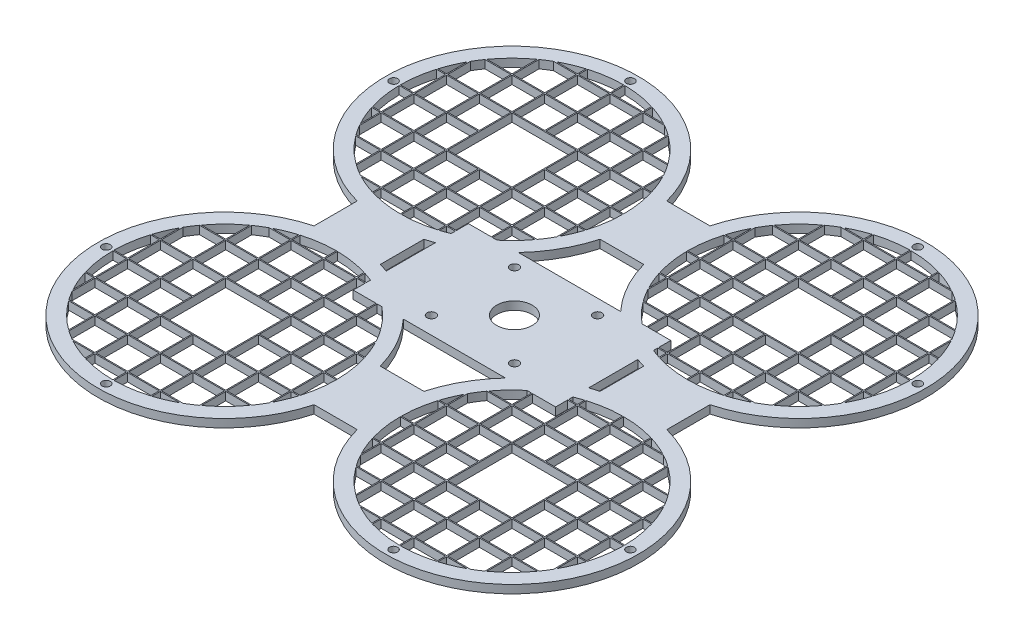
SolidWorks part; units mm, degrees
ref_plane "Front Plane" through (0, 0, 0) normal (0, 0, 1) x (1, 0, 0)
ref_plane "Top Plane" through (0, 0, 0) normal (0, 1, 0) x (1, 0, 0)
ref_plane "Right Plane" through (0, 0, 0) normal (1, 0, 0) x (0, 0, -1)
sketch "Sketch2" plane through (0, 0, 0) normal (0, 1, 0) x (1, 0, 0)
  circle A1 centre (0, 0) radius 41
  circle A2 centre (0, 0) radius 46
  point P208 (0, 0)
extrude "Boss-Extrude2" add sketch "Sketch2" along normal blind 3
sketch "Sketch4" plane through (0, 3, 0) normal (0, 1, 0) x (1, 0, 0)
  line L0 (0, 46) -> (0, 12)
  line L1 (12, 44.4072) -> (12, -44.4072)
  line L2 (24, 39.2428) -> (24, -39.2428)
  line L3 (36, 28.6356) -> (36, -28.6356)
  line L4 (-12, 44.4072) -> (-12, -44.4072)
  line L5 (-24, 39.2428) -> (-24, -32)
  line L6 (-36, 28.6356) -> (-36, -28.6356)
  line L7 (-46, 0) -> (-12, 0)
  line L8 (-44.4072, -12) -> (44.4072, -12)
  line L9 (-39.2428, -24) -> (39.2428, -24)
  line L10 (12, 0) -> (46, 0)
  line L11 (-44.4072, 12) -> (44.4072, 12)
  line L12 (-39.2428, 24) -> (39.2428, 24)
  line L13 (-28.6356, 36) -> (28.6356, 36)
  line L14 (-16, -36) -> (28.6356, -36)
  line L15 (0, -12) -> (0, -46)
  line L50 (-26.0661, -32) -> (-16, -32)
  line L52 (-26.0661, -32) -> (-26.0661, -37.902)
  line L60 (-16, -32) -> (-16, -43.1277)
  line L61 (-28.6356, -36) -> (-26.0661, -36) [skipped]
  circle A1 centre (0, 0) radius 46 construction
  circle A2 centre (0, 0) radius 46
  dimension "D1" = 4
  dimension "D2" = 4
extrude "Extrude-Thin5" add sketch "Sketch4" against normal blind 3 thin thin type one direction wall 0.4
sketch "Sketch5" plane through (0, 0, 0) normal (0, -1, 0) x (1, 0, 0)
  circle A0 centre (0, -43.4524) radius 1.5
  circle A3 centre (43.4524, 0) radius 1.5
  circle A4 centre (0, 43.4524) radius 1.5 [skipped]
  circle A5 centre (-43.4524, 0) radius 1.5 [skipped]
  point P11 (0, 0)
  dimension "D1" = 4
extrude "Cut-Extrude1" cut sketch "Sketch5" against normal blind 3
sketch "Sketch8" plane through (0, 3, 0) normal (0, 1, 0) x (1, 0, 0)
  line L1 (-16, -32) -> (-25.632, -32)
  line L2 (-16, -32) -> (-16, -37.7492)
  line L3 (-16, -37.7492) -> (-25.632, -37.7492)
  line L4 (-25.632, -32) -> (-25.632, -37.7492)
extrude "Boss-Extrude4" add sketch "Sketch8" against normal through all
sketch "Sketch9" plane through (0, 3, 0) normal (0, 1, 0) x (1, 0, 0)
  circle A3 centre (-22.2697, -36.1812) radius 2.25
extrude "Cut-Extrude3" cut sketch "Sketch9" against normal through all
ref_plane "Plane1" through (-52.73, 0, 0) normal (1, 0, 0) x (0, 0, -1)
mirror "Mirror1" about plane through (-52.73, 0, 0) normal (1, 0, 0) of bodies 159
sketch "Sketch10" plane through (0, 3, 0) normal (0, 1, 0) x (1, 0, 0)
  line L0 (-66.2554, 12) -> (-69.06, 12) construction
  line L1 (-63.5152, 12) -> (-41.7915, 12)
  line L2 (-63.5152, 12) -> (-63.5152, -12.4)
  line L3 (-63.5152, -12.4) -> (-41.7915, -12.4)
  line L4 (-41.7915, 12) -> (-41.7915, -12.4)
  line L5 (-66.3801, -12.4) -> (-69.06, -12.4) construction
extrude "Boss-Extrude5" add sketch "Sketch10" against normal up to surface (3 mm away) up to face at (-22.2697, 0, 38.4312)
ref_plane "Plane2" through (0, 0, 52.73) normal (0, 0, 1) x (1, 0, 0)
mirror "Mirror2" about plane through (0, 0, 52.73) normal (0, 0, 1) of bodies 177
sketch "Sketch11" plane through (0, 3, 0) normal (0, 1, 0) x (1, 0, 0)
  line L0 (-93.06, -36.4) -> (-93.06, -39.0799) construction
  line L1 (-117.46, -41.6571) -> (-93.06, -41.6571)
  line L2 (-117.46, -41.6571) -> (-117.46, -63.409)
  line L3 (-117.46, -63.409) -> (-93.06, -63.409)
  line L4 (-93.06, -41.6571) -> (-93.06, -63.409)
  line L5 (-117.46, -36.4) -> (-117.46, -39.2046) construction
extrude "Boss-Extrude6" add sketch "Sketch11" against normal up to surface (3 mm away) up to face at (-52.73, 0, -0.0036)
sketch "Sketch12" plane through (0, 3, 0) normal (0, 1, 0) x (1, 0, 0)
  line L0 (12, -36.4) -> (12, -39.2046) construction
  line L1 (-12.4, -42.0227) -> (12, -42.0227)
  line L2 (-12.4, -42.0227) -> (-12.4, -63.5098)
  line L3 (-12.4, -63.5098) -> (12, -63.5098)
  line L4 (12, -42.0227) -> (12, -63.5098)
  line L5 (-12.4, -36.4) -> (-12.4, -39.0799) construction
extrude "Boss-Extrude7" add sketch "Sketch12" against normal up to surface (3 mm away) up to face at (-62.5401, 0, 52.73)
sketch "Sketch13" plane through (0, 0, 0) normal (0, -1, 0) x (1, 0, 0)
  line L1 (-89.86, 73.86) -> (-15.6, 73.86)
  line L2 (-89.86, 73.86) -> (-89.86, 31.6)
  line L3 (-89.86, 31.6) -> (-15.6, 31.6)
  line L4 (-15.6, 73.86) -> (-15.6, 31.6)
extrude "Boss-Extrude8" add sketch "Sketch13" against normal up to surface (3 mm away) up to face at (-52.73, 3, 52.73)
sketch "Sketch14" plane through (0, 0, 0) normal (0, -1, 0) x (1, 0, 0)
  circle A0 centre (-52.2696, 52.2786) radius 6.495 construction
  circle A1 centre (-52.2696, 52.2786) radius 6.495
extrude "Cut-Extrude4" cut sketch "Sketch14" against normal up to next
sketch "Sketch15" plane through (0, 0, 0) normal (0, -1, 0) x (1, 0, 0)
  circle A0 centre (-37.0195, 37.0287) radius 1.6 construction
  circle A1 centre (-67.5195, 37.0285) radius 1.6 construction
  circle A2 centre (-67.5197, 67.5285) radius 1.6 construction
  circle A3 centre (-37.0197, 67.5287) radius 1.6 construction
  circle A4 centre (-37.0195, 37.0287) radius 1.6
  circle A5 centre (-67.5195, 37.0285) radius 1.6
  circle A6 centre (-67.5197, 67.5285) radius 1.6
  circle A7 centre (-37.0197, 67.5287) radius 1.6
extrude "Cut-Extrude5" cut sketch "Sketch15" against normal up to next
